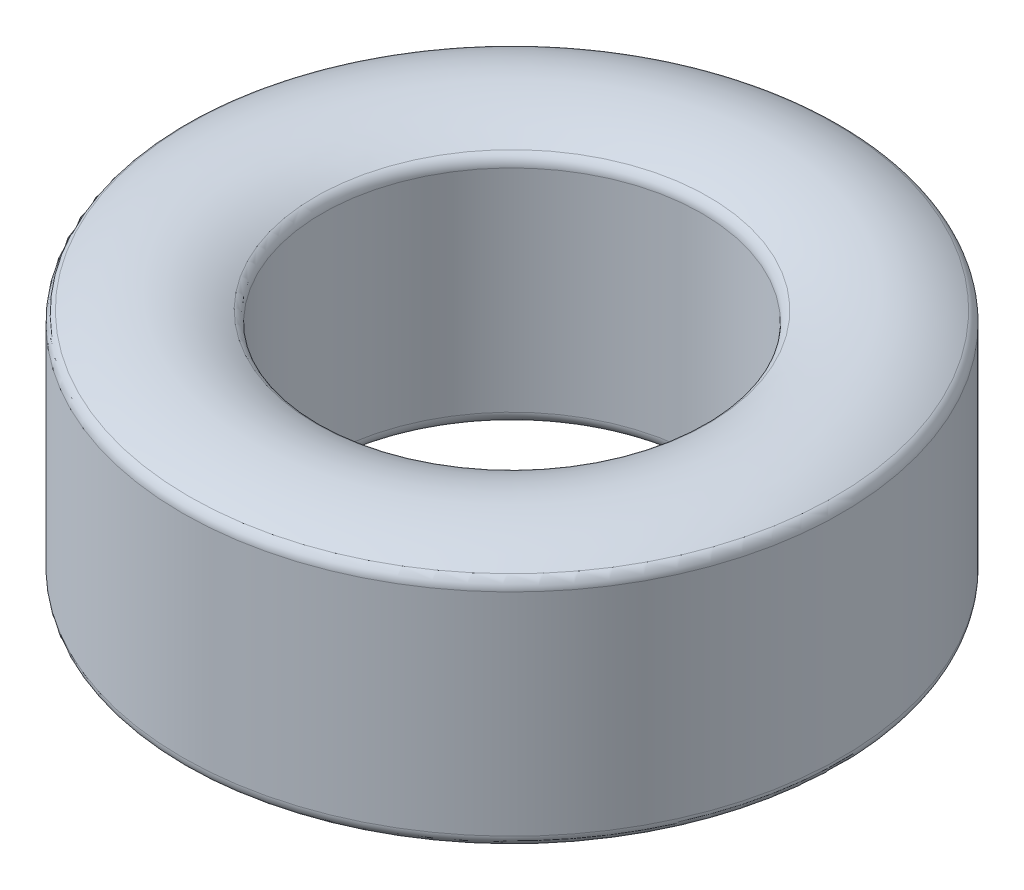
SolidWorks part; units mm, degrees
ref_plane "Front Plane" through (0, 0, 0) normal (0, 0, 1) x (1, 0, 0)
ref_plane "Top Plane" through (0, 0, 0) normal (0, 1, 0) x (1, 0, 0)
ref_plane "Right Plane" through (0, 0, 0) normal (1, 0, 0) x (0, 0, -1)
sketch "Sketch1" plane through (0, 0, 0) normal (1, 0, 0) x (0, 0, -1)
  line L0 (0, 59.1222) -> (0, -46.6086) construction
  line L1 (-7.5, 4.1779) -> (-7.5, -4.1779)
  line L2 (-13.02, 4.1779) -> (-13.02, -4.1779)
  line L3 (-20.8257, 5.25) -> (-1.7185, 5.25) construction
  line L4 (-39.1478, 0) -> (37.4253, 0) construction
  arc A0 (-12.7579, 4.6177) -> (-7.7621, 4.6177) centre (-10.26, 0) cw
  arc A1 (-12.7579, -4.6177) -> (-7.7621, -4.6177) centre (-10.26, 0) ccw
  arc A2 (-7.5, -4.1779) -> (-7.7621, -4.6177) centre (-8, -4.1779) cw
  arc A3 (-13.02, -4.1779) -> (-12.7579, -4.6177) centre (-12.52, -4.1779) ccw
  arc A4 (-7.7621, 4.6177) -> (-7.5, 4.1779) centre (-8, 4.1779) cw
  arc A5 (-13.02, 4.1779) -> (-12.7579, 4.6177) centre (-12.52, 4.1779) cw
  point P10 (-7.5, 0)
  point P19 (-7.5, -4.466)
  point P22 (-13.02, -4.466)
  point P25 (-7.5, 4.466)
  point P28 (-13.02, 4.466)
  dimension "D1" = 5.25
  dimension "D4" = 0.5
  dimension "D2" = 5.52
  dimension "D3" = 15
revolve "Revolve1" add sketch "Sketch1" angle 360 about L0
